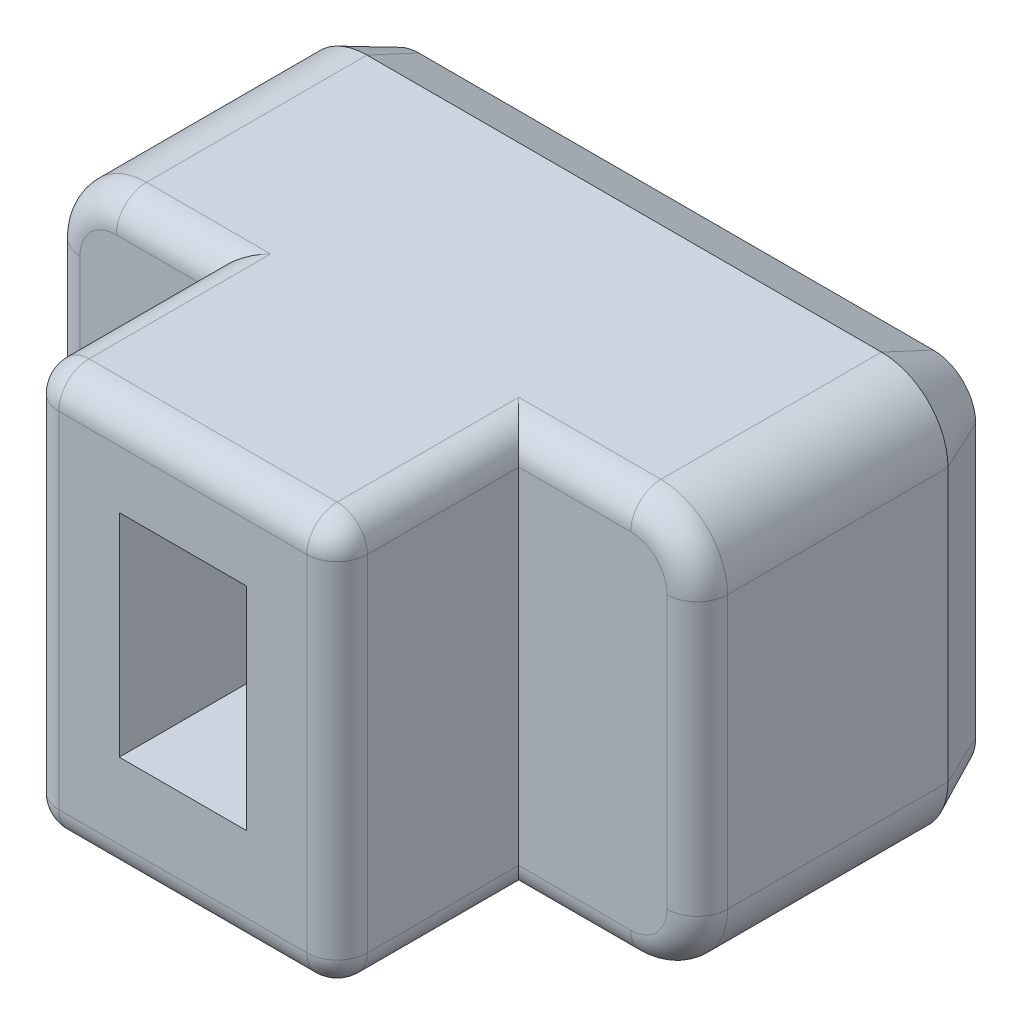
SolidWorks part; units mm, degrees
ref_plane "Plan de face" through (0, 0, 0) normal (0, 0, 1) x (1, 0, 0)
ref_plane "Plan de dessus" through (0, 0, 0) normal (0, 1, 0) x (1, 0, 0)
ref_plane "Plan de droite" through (0, 0, 0) normal (1, 0, 0) x (0, 0, -1)
sketch "Esquisse2" plane through (0, 0, 0) normal (0, 0, 1) x (1, 0, 0)
  line L1 (1.1, 0) -> (9.6, 0)
  line L2 (0, 1.1) -> (0, 5.6)
  line L3 (1.1, 6.7) -> (9.6, 6.7)
  line L4 (10.7, 1.1) -> (10.7, 5.6)
  arc A0 (9.6, 6.7) -> (10.7, 5.6) centre (9.6, 5.6) cw
  arc A1 (9.6, 0) -> (10.7, 1.1) centre (9.6, 1.1) ccw
  arc A2 (1.1, 0) -> (0, 1.1) centre (1.1, 1.1) cw
  arc A3 (0, 5.6) -> (1.1, 6.7) centre (1.1, 5.6) cw
  point P7 (10.7, 6.7)
  point P12 (0, 0)
  point P15 (0, 6.7)
  dimension "D3" = 1.1
  dimension "D1" = 10.7
  dimension "D2" = 6.7
extrude "Boss.-Extru.1" add sketch "Esquisse2" along normal blind 8
sketch "Esquisse3" plane through (0, 0, 8) normal (0, 0, 1) x (1, 0, 0)
  line L0 (0, 5.6) -> (0, 1.1) construction
  line L1 (4.15, 5.25) -> (6.25, 5.25)
  line L2 (4.15, 5.25) -> (4.15, 1.75)
  line L3 (4.15, 1.75) -> (6.25, 1.75)
  line L4 (6.25, 5.25) -> (6.25, 1.75)
  line L5 (10.7, 1.1) -> (10.7, 5.6) construction
  line L6 (9.6, 6.7) -> (1.1, 6.7) construction
  line L7 (1.1, 0) -> (9.6, 0) construction
  dimension "D1" = 2.1
  dimension "D2" = 3.5
  dimension "D3" = 4.15
  dimension "D4" = 4.45
  dimension "D5" = 1.45
  dimension "D6" = 1.75
extrude "Enlèv. mat.-Extru.1" cut sketch "Esquisse3" against normal blind 3
sketch "Esquisse4" plane through (0, 0, 8) normal (0, 0, 1) x (1, 0, 0)
  line L0 (2.65, 6.7) -> (2.65, 0)
  line L1 (9.6, 6.7) -> (1.1, 6.7) construction
  line L2 (1.1, 0) -> (9.6, 0) construction
  line L3 (2.65, 0) -> (7.75, 0)
  line L4 (7.75, 0) -> (7.75, 6.7)
  line L5 (7.75, 6.7) -> (2.65, 6.7)
  line L6 (4.15, 5.25) -> (4.15, 1.75) construction
  line L7 (6.25, 1.75) -> (6.25, 5.25) construction
  dimension "D1" = 1.5
  dimension "D2" = 1.5
extrude "Enlèv. mat.-Extru.2" cut sketch "Esquisse4" against normal blind 3 flip side to cut
fillet "Congé1" radius 0.5 18 edges at (8.675, 0, 5) (10.3778, 0.3222, 5) (10.7, 3.35, 5) (10.3778, 6.3778, 5) (1.875, 6.7, 5) (0.3222, 6.3778, 5) (1.875, 0, 5) (0.3222, 0.3222, 5) (7.75, 6.7, 6.5) (2.65, 6.7, 6.5) (7.75, 0, 6.5) (2.65, 0, 6.5) (2.65, 3.35, 8) (5.2, 6.7, 8) (7.75, 3.35, 8) (5.2, 0, 8) (8.675, 6.7, 5) (0, 3.35, 5)
chamfer "Chanfrein1" distance 0.4 angle 65 8 edges at (5.35, 0, 0) (10.3778, 0.3222, 0) (0.3222, 0.3222, 0) (10.7, 3.35, 0) (0, 3.35, 0) (10.3778, 6.3778, 0) (0.3222, 6.3778, 0) (5.35, 6.7, 0) first distance on face at (5.35, 3.35, 0)
sketch "Esquisse5" plane through (0, 0, 0) normal (0, 0, 1) x (1, 0, 0)
  line L0 (-0.9378, 5.093) -> (11.6517, 5.093) construction
  text T0 "D->" font "Corbel" height 3.5
extrude "Enlèv. mat.-Extru.3" cut sketch "Esquisse5" along normal blind 0.2
extrude "Boss.-Extru.2" add sketch "Esquisse5<4>" against normal blind 0.2
sketch "Esquisse5<4>" plane through (0, 0, 0) normal (0, 0, 1) x (1, 0, 0) same geometry as "Esquisse5"
